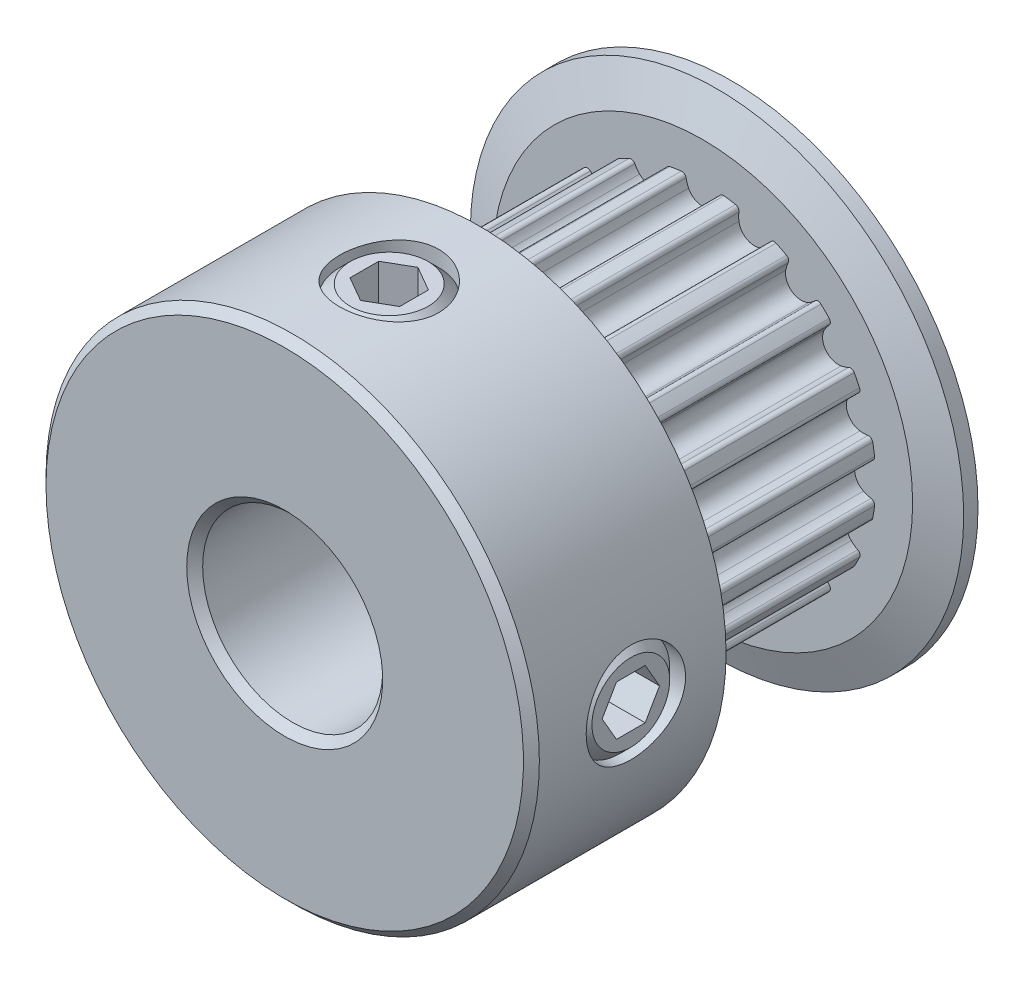
SolidWorks part; units mm, degrees
ref_plane "Front Plane" through (0, 0, 0) normal (0, 0, 1) x (1, 0, 0)
ref_plane "Top Plane" through (0, 0, 0) normal (0, 1, 0) x (1, 0, 0)
ref_plane "Right Plane" through (0, 0, 0) normal (1, 0, 0) x (0, 0, -1)
sketch "Sketch1" plane through (0, 0, 0) normal (0, 0, 1) x (1, 0, 0)
  line L1 (-1.7499, 5.3585) -> (1.7499, 5.3585) construction
  line L4 (0, 0) -> (0, 5.3585) construction
  line L5 (0, 5.3585) -> (0, 11.2119) construction
  line L6 (0, 6.3625) -> (1.9751, 6.0482) construction
  line L7 (1.9751, 6.0482) -> (2.6648, 5.8229) construction
  line L8 (1.9751, 6.0482) -> (1.7499, 5.3585) construction
  line L9 (-1.9751, 6.0482) -> (-1.7499, 5.3585) construction
  line L10 (-1.8963, 5.8067) -> (-2.841, 8.6995)
  line L11 (-2.841, 8.6995) -> (2.841, 8.6995)
  line L12 (2.841, 8.6995) -> (1.8963, 5.8067)
  circle A0 centre (0, 0) radius 6.3625 construction
  circle A1 centre (0, 0) radius 8.6995 construction
  circle A2 centre (0, 0) radius 6.1085 construction
  arc A3 (-0.4989, 5.6703) -> (0.4989, 5.6703) centre (0, 5.9135) ccw
  arc A4 (-0.4989, 5.6703) -> (-0.5855, 5.9387) centre (0.4, 6.1085) cw
  arc A5 (-1.8963, 5.8067) -> (-0.7518, 6.0621) centre (0, 0) cw
  arc A6 (-0.5855, 5.9387) -> (-0.7518, 6.0621) centre (-0.7333, 5.9132) ccw
  arc A7 (1.8963, 5.8067) -> (0.7518, 6.0621) centre (0, 0) ccw
  arc A8 (0.5855, 5.9387) -> (0.7518, 6.0621) centre (0.7333, 5.9132) cw
  arc A9 (0.4989, 5.6703) -> (0.5855, 5.9387) centre (-0.4, 6.1085) ccw
  point P6 (0, 20.9083)
  point P11 (0, 6.3625)
  point P13 (0, 8.6995)
  point P14 (0, 6.1085)
  dimension "D1" = 9.6964
  dimension "D2" = 4.8494
sketch "Sketch2" plane through (0, 0, 0) normal (1, 0, 0) x (0, 0, -1)
  line L0 (-7.875, 3.175) -> (7.875, 3.175)
  line L1 (-7.875, 3.175) -> (-7.875, 8.6995)
  line L2 (-1.01, 8.6995) -> (-7.875, 8.6995)
  line L3 (-1.515, 3.175) -> (-1.515, 8.6995) construction
  line L4 (-1.515, 8.6995) -> (-0.505, 8.6995) construction
  line L5 (-0.505, 8.6995) -> (-0.505, 6.1085) construction
  line L6 (-0.505, 6.1085) -> (6.865, 6.1085)
  line L7 (6.865, 6.1085) -> (6.865, 8.6995) construction
  line L8 (6.865, 8.6995) -> (7.875, 8.6995) construction
  line L9 (7.875, 8.6995) -> (7.875, 3.175)
  line L10 (-7.875, 0) -> (7.875, 0) construction
  line L11 (7.37, 8.6995) -> (6.865, 7.404)
  line L12 (-0.505, 7.404) -> (-1.01, 8.6995)
  line L14 (-0.505, 7.404) -> (-0.505, 6.1085)
  line L15 (6.865, 6.1085) -> (6.865, 7.404)
  line L16 (7.37, 8.6995) -> (7.875, 8.6995)
  arc A0 (-0.505, 7.404) -> (-1.01, 8.6995) centre (-2.4192, 7.404) ccw construction
  arc A1 (6.865, 7.404) -> (7.37, 8.6995) centre (8.7792, 7.404) cw construction
  point P12 (-0.505, 7.404)
  point P14 (-1.01, 8.6995)
  point P20 (6.865, 7.404)
  point P21 (7.37, 8.6995)
  point P25 (6.865, 0)
  point P26 (-0.505, 0)
  dimension "OA" = 15.75
  dimension "Bore" = 6.35
  dimension "Outside Width" = 8.38
  dimension "Inside Width" = 7.37
revolve "Revolve1" add sketch "Sketch2" angle 360 mid plane about L10
sketch "Sketch3" plane through (0, 0, 0) normal (0, 0, 1) x (1, 0, 0)
  line L6 (2.841, 8.6995) -> (-2.841, 8.6995)
  line L7 (1.8963, 5.8067) -> (2.841, 8.6995)
  line L8 (-2.841, 8.6995) -> (-1.8963, 5.8067)
  line L9 (2.841, 8.6995) -> (-2.841, 8.6995)
  line L10 (1.8963, 5.8067) -> (2.841, 8.6995)
  line L11 (-2.841, 8.6995) -> (-1.8963, 5.8067)
  arc A8 (1.8963, 5.8067) -> (0.7518, 6.0621) centre (0, 0) ccw
  arc A9 (0.7518, 6.0621) -> (0.5855, 5.9387) centre (0.7333, 5.9132) ccw
  arc A10 (0.4989, 5.6703) -> (0.5855, 5.9387) centre (-0.4, 6.1085) ccw
  arc A11 (-0.4989, 5.6703) -> (0.4989, 5.6703) centre (0, 5.9135) ccw
  arc A12 (-0.5855, 5.9387) -> (-0.4989, 5.6703) centre (0.4, 6.1085) ccw
  arc A13 (-0.5855, 5.9387) -> (-0.7518, 6.0621) centre (-0.7333, 5.9132) ccw
  arc A14 (-0.7518, 6.0621) -> (-1.8963, 5.8067) centre (0, 0) ccw
  arc A15 (1.8963, 5.8067) -> (0.7518, 6.0621) centre (0, 0) ccw
  arc A16 (0.7518, 6.0621) -> (0.5855, 5.9387) centre (0.7333, 5.9132) ccw
  arc A17 (0.4989, 5.6703) -> (0.5855, 5.9387) centre (-0.4, 6.1085) ccw
  arc A18 (-0.4989, 5.6703) -> (0.4989, 5.6703) centre (0, 5.9135) ccw
  arc A19 (-0.5855, 5.9387) -> (-0.4989, 5.6703) centre (0.4, 6.1085) ccw
  arc A20 (-0.5855, 5.9387) -> (-0.7518, 6.0621) centre (-0.7333, 5.9132) ccw
  arc A21 (-0.7518, 6.0621) -> (-1.8963, 5.8067) centre (0, 0) ccw
  dimension "D1" = 0
extrude "Cut-Extrude1" cut sketch "Sketch3" against normal up to vertex (6.865 mm away) from vertex up to point (0, 6.1085, -6.865) starting at point (0, 6.1085, 0.505)
pattern_circular "CirPattern1" count 20 over 360 about axis through (0, 0, 7.875) along (0, 0, 1) of "Cut-Extrude1"
sketch "Sketch4" plane through (0, 0, 0) normal (1, 0, 0) x (0, -1, 0)
  line L0 (0, -0.505) -> (0, -7.875) construction
  line L1 (-3.175, -7.875) -> (3.175, -7.875) construction
  line L2 (7.404, -0.505) -> (-7.404, -0.505) construction
  circle A0 centre (0, -4.19) radius 1.7526
extrude "Cut-Extrude2" cut sketch "Sketch4" along normal through all
ref_plane "Plane1" through (0, 0, 4.19) normal (0, 0, 1) x (1, 0, 0)
sketch "Sketch5" plane through (0, 0, 4.19) normal (0, 0, 1) x (1, 0, 0)
  line L0 (0, 0) -> (0, 8.6995) construction
  line L1 (3.175, -1.3716) -> (3.175, 0)
  line L2 (3.556, -1.7526) -> (8.1401, -1.7526)
  line L3 (3.175, 0) -> (8.6995, 0) construction
  line L4 (3.175, 0) -> (8.5211, 0)
  line L5 (8.5211, 0) -> (8.5211, -1.3716)
  line L6 (3.556, -1.7526) -> (3.175, -1.3716)
  line L7 (8.5211, -1.3716) -> (8.1401, -1.7526)
  circle A0 centre (0, 0) radius 8.6995 construction
  circle A1 centre (0, 0) radius 3.175 construction
  point P2 (3.175, -1.7526)
  point P11 (8.5211, -1.7526)
revolve "Revolve2" add sketch "Sketch5" angle 360 mid plane about L4
sketch "Sketch6" plane through (8.5211, 5.3841, 0) normal (-1, 0, 0) x (0, -1, 0)
  line L1 (5.3841, 5.2019) -> (4.5078, 4.6959)
  line L2 (4.5078, 4.6959) -> (4.5078, 3.6841)
  line L3 (4.5078, 3.6841) -> (5.3841, 3.1781)
  line L4 (5.3841, 3.1781) -> (6.2604, 3.6841)
  line L5 (6.2604, 3.6841) -> (6.2604, 4.6959)
  line L6 (6.2604, 4.6959) -> (5.3841, 5.2019)
  circle A0 centre (5.3841, 4.19) radius 0.8763 construction
  dimension "D1" = 1.7526
extrude "Cut-Extrude3" cut sketch "Sketch6" along normal blind 1.3144
pattern_circular "CirPattern3" count 2 over 90 about axis through (0, 0, 7.875) along (0, 0, 1) of "Cut-Extrude2", "Revolve2", "Cut-Extrude3"
chamfer "Chamfer1" distance 0.2807 angle 45 2 edges at (3.175, 0, 7.875) (8.6995, 0, 7.875)
ref_axis "Center Axis 1" through (0, 0, -7.875) along (0, 0, 1)
ref_plane "Contact Plane 1" through (0, 0, 7.875) normal (0, 0, 1) x (1, 0, 0)
ref_plane "Contact Plane 2" through (0, 0, -7.875) normal (0, 0, -1) x (-1, 0, 0)
equation "\"D2@Sketch1\"= \"D1@Sketch1\" / 2"
equation "\"D1@Sketch6\" = \"Set Screw@Sketch4\" / 2"
equation "\"D1@Cut-Extrude3\" = \"D1@Sketch6\"*.75"
